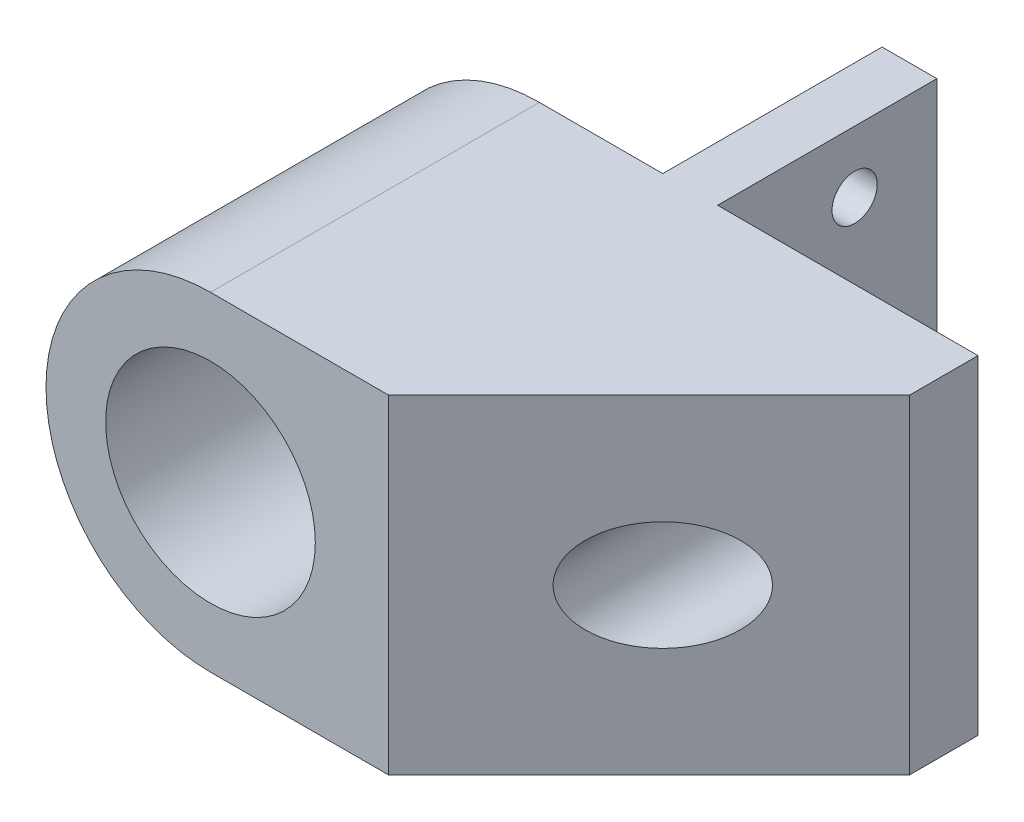
SolidWorks part; units mm, degrees
ref_plane "Plano frontal" through (0, 0, 0) normal (0, 0, 1) x (1, 0, 0)
ref_plane "Plano superior" through (0, 0, 0) normal (0, 1, 0) x (1, 0, 0)
ref_plane "Plano direito" through (0, 0, 0) normal (1, 0, 0) x (0, 0, -1)
sketch "Esboço1" plane through (0, 0, 0) normal (0, 0, 1) x (1, 0, 0)
  line L0 (0, 0) -> (-19, 0)
  line L1 (-23, 0) -> (-23, 6)
  line L2 (-32, -24) -> (-23, -24)
  line L3 (0, -24) -> (0, 0)
  line L4 (-23, 6) -> (-19, 6)
  line L5 (-19, 6) -> (-19, 0)
  line L6 (-32, -12) -> (-24.5731, -12) construction
  line L7 (-19, -30) -> (-19, -24)
  line L8 (-23, -30) -> (-19, -30)
  line L9 (-23, -24) -> (-23, -30)
  line L10 (-23, 0) -> (-32, 0)
  line L11 (-19, -24) -> (0, -24)
  arc A0 (-32, 0) -> (-32, -24) centre (-32, -12) ccw
  circle A1 centre (-32, -12) radius 7.65
  circle A2 centre (-9, -12) radius 1.6
  point P10 (0, -12)
  point P19 (-25.926, 5.2348)
  point P20 (-19.4437, 6)
  dimension "D1" = 15.3
  dimension "D5" = 3.2
  dimension "D2" = 32
  dimension "D3" = 24
  dimension "D4" = 9
  dimension "D6" = 10
  dimension "D7" = 6
  dimension "D8" = 4
extrude "Ressalto-extrusão1" add sketch "Esboço1" along normal blind 40
sketch "Esboço2" plane through (0, 0, 0) normal (0, 1, 0) x (1, 0, 0)
  line L1 (0, -40) -> (-19, -40)
  line L2 (0, -40) -> (0, -20)
  line L3 (0, -20) -> (-19, -20)
  line L4 (-19, -40) -> (-19, -20)
  line L6 (-23, -40) -> (-23, 0) construction
  line L7 (-44, 0) -> (-23, 0)
  line L8 (-44, 0) -> (-44, -16)
  line L9 (-44, -16) -> (-23, -16)
  line L10 (-23, 0) -> (-23, -16)
  line L11 (0, 0) -> (-19, 0)
  line L12 (0, 0) -> (0, -16)
  line L13 (0, -16) -> (-19, -16)
  line L14 (-19, 0) -> (-19, -16)
  line L15 (-19, -40) -> (-19, 0) construction
  line L16 (-19, -40) -> (-19, 0) construction
  line L17 (-44, -40) -> (-32, -40) construction
  point P7 (-19, -16)
  point P17 (-23, -16)
  point P20 (-19, -12)
  dimension "D1" = 24
  dimension "D3" = 4
extrude "Corte-extrusão1" cut sketch "Esboço2" against normal through all
sketch "Esboço3" plane through (-23, 0, 0) normal (-1, 0, 0) x (0, 0, 1)
  line L0 (0, -12) -> (16, -12) construction
  line L1 (0, 6) -> (0, -30) construction
  line L2 (16, -24) -> (16, 0) construction
  line L3 (0, -16) -> (16, -16) construction
  line L4 (0, -8) -> (16, -8) construction
  line L6 (0, 6) -> (40, 6)
  line L7 (0, 6) -> (0, 0)
  line L8 (0, 0) -> (40, 0)
  line L9 (40, 6) -> (40, 0)
  line L10 (40, -24) -> (0, -24)
  line L11 (40, -24) -> (40, -30)
  line L12 (40, -30) -> (0, -30)
  line L13 (0, -24) -> (0, -30)
  circle A0 centre (6, -4.5) radius 1.65
  circle A1 centre (6, -19.5) radius 1.65
  dimension "D3" = 3.3
  dimension "D4" = 15
  dimension "D5" = 10
  dimension "D1" = 4
  dimension "D2" = 4
extrude "Corte-extrusão2" cut sketch "Esboço3" against normal blind 20
chamfer "Chanfro2" distance 20 angle 45 1 edges at (-19, -12, 20)
sketch "Esboço4" plane through (0, 0, 40) normal (0, 0, 1) x (1, 0, 0)
  circle A0 centre (-9, -12) radius 4
  dimension "D1" = 8
extrude "Corte-extrusão3" cut sketch "Esboço4" against normal up to vertex (19 mm away) up to point (0, 0, 21)
